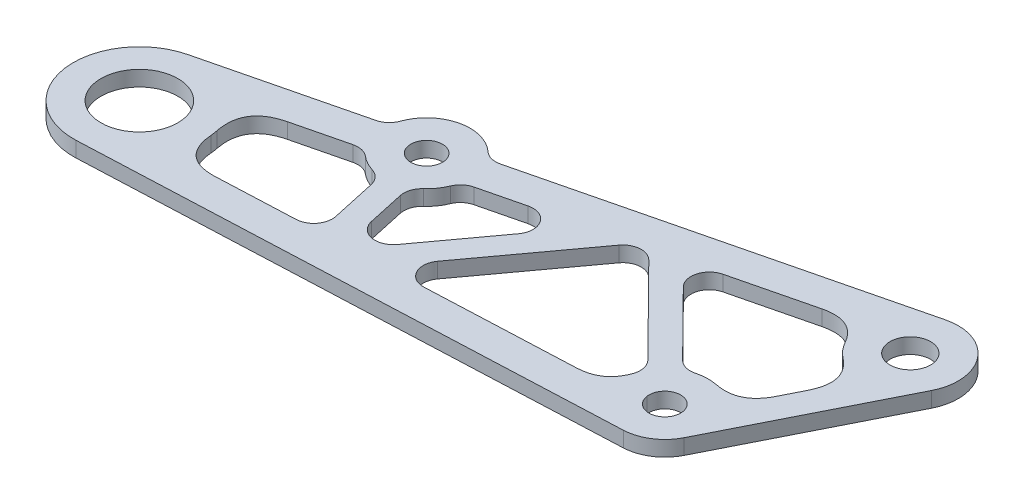
SolidWorks part; units mm, degrees
material "6061-T6 (SS)"
ref_plane "Front Plane" through (0, 0, 0) normal (0, 0, 1) x (1, 0, 0)
ref_plane "Top Plane" through (0, 0, 0) normal (0, 1, 0) x (1, 0, 0)
ref_plane "Right Plane" through (0, 0, 0) normal (1, 0, 0) x (0, 0, -1)
sketch "Sketch1" plane through (0, 0, 0) normal (0, 1, 0) x (1, 0, 0)
  line L0 (0, 0) -> (124.8778, 34.4406) construction
  line L1 (124.8778, 34.4406) -> (108.585, 0) construction
  line L2 (108.585, 0) -> (0, 0) construction
  line L3 (-3.2476, 13.2606) -> (122.5214, 44.0623)
  line L5 (116.6057, -4.036) -> (133.7266, 29.9879)
  line L6 (108.585, 0) -> (109.8191, -8.8937) construction
  line L7 (-1.8881, 7.7097) -> (123.8808, 38.5113)
  line L8 (111.5006, -1.4671) -> (128.6215, 32.5568)
  line L9 (0.3416, -7.9301) -> (108.7255, -3.2609)
  line L10 (108.585, 0) -> (80.9067, 27.9867) construction
  line L11 (108.585, 0) -> (108.585, 29.9472) construction
  line L12 (74.1927, 26.3424) -> (50.6623, -5.7623) construction
  line L13 (78.0308, 27.2823) -> (53.9142, -5.6222)
  line L14 (70.3546, 25.4024) -> (47.4105, -5.9024)
  line L15 (78.0308, 27.2823) -> (100.7231, 4.3373)
  line L16 (83.7825, 28.691) -> (104.3351, 7.9094)
  line L17 (62.4275, 10.29) -> (60.3789, 11.7916) construction
  line L18 (62.4275, 10.29) -> (64.4762, 8.7885) construction
  line L19 (94.7458, 13.9933) -> (92.9399, 12.2073) construction
  line L20 (94.7458, 13.9933) -> (96.5518, 15.7794) construction
  line L21 (114.3014, 6.9241) -> (123.2323, 24.6722)
  line L22 (0.5876, -13.6398) -> (108.9715, -8.9706)
  line L23 (9.9856, 9.3101) -> (114.9891, 35.0261)
  line L24 (12.1896, -6.1485) -> (99.9242, -2.3689)
  line L25 (12.626, 31.0376) -> (39.0947, 20.2702) construction
  line L26 (12.626, 31.0376) -> (0, 0) construction
  line L27 (39.0947, 20.2702) -> (44.8348, -6.0133) construction
  line L28 (43.4137, 12.3983) -> (47.4105, -5.9024)
  line L29 (-819.3721, 46.7661) -> (-738.0185, 246.752) construction
  line L30 (38.4507, 11.3144) -> (42.2592, -6.1243)
  line L31 (-176324.9257, 71613.2166) -> (174939.7278, -71280.061) construction
  circle A0 centre (0, 0) radius 7.9375
  circle A1 centre (124.8778, 34.4406) radius 4.191
  circle A2 centre (108.585, 0) radius 3.2639
  circle A3 centre (0, 0) radius 13.6525
  circle A4 centre (108.585, 0) radius 8.9789
  circle A5 centre (124.8778, 34.4406) radius 9.906
  arc A6 (-3.2476, 13.2606) -> (6.5337, -11.9876) centre (0, 0) ccw
  arc A7 (116.6057, -4.036) -> (108.585, -8.9789) centre (108.585, 0) cw
  arc A8 (122.5214, 44.0623) -> (133.7266, 29.9879) centre (124.8778, 34.4406) cw
  circle A9 centre (39.0947, 20.2702) radius 3.2639
  circle A10 centre (39.0947, 20.2702) radius 8.9789
  dimension "D4" = 15.875
  dimension "D5" = 6.5278
  dimension "D6" = 8.382
  dimension "D7" = 5.715
  dimension "D8" = 5.715
  dimension "D9" = 5.715
  dimension "D18" = 17.9578
  dimension "D19" = 6.5278
  dimension "D1" = 129.54
  dimension "D2" = 38.1
  dimension "D3" = 108.585
  dimension "D10" = 97.9
  dimension "D11" = 70
  dimension "D12" = 40
  dimension "D13" = 5.08
  dimension "D14" = 1.27
  dimension "D15" = 1.27
  dimension "D16" = 1.27
  dimension "D17" = 28.575
  dimension "D20" = 2.54
  dimension "D21" = 5.08
extrude "Boss-Extrude4" add sketch "Sketch1" against normal blind 3.175 contours A5 L7 A1 L8 | A5 L3 A3 L7 | A3 L9 A0 L7 | L9 A3 L7 A0 | A3 L9 L14 L24 | A4 L9 A3 L22 | A4 L24 L13 L9 | L24 L14 L9 L13 | A4 L16 L23 L15 | L14 L23 L13 L7 | L15 L23 L16 L7 | A5 L7 L16 L23 | A5 L8 A4 L5 | L7 A5 L8 A1 | A4 L8 A2 L9 | L8 A4 L9 A2 | L7 A10 | A10 L23 L14 L7 | L14 L24 L13 L23 | A10 L30 L24 L28 | L24 L30 L9 L28 | A10 L23 A9 | L7 A10 L23 A9 | A10 L7 A3 L23 | A10 L3 A3 L7 | L3 A10 | L7 A10 L3 A9 region at (3.0925, 0, -12.9166) region at (17.5549, 0, -15.5789) region at (37.7563, 0, -25.7353) region at (33.4097, 0, -19.3627) region at (55.5019, 0, 8.4889) region at (9.0069, 0, -1.2841) region at (20.5523, 0, -12.5533) region at (44.5556, 0, -22.0924) region at (82.2682, 0, -31.3107) region at (34.4779, 0, -16.435) region at (110.8898, 0, 3.5657) region at (130.8206, 0, -42.0146) region at (40.4953, 0, -14.5512) region at (122.752, 0, -13.9922) region at (26.9756, 0, 6.1507) region at (99.6799, 0, -31.9349) region at (120.3421, 0, -30.8296) region at (58.8928, 0, -21.9466) region at (42.7943, 0, -3.4344) region at (106.4195, 0, -3.3502) region at (77.2616, 0, 3.984) region at (44.6973, 0, 5.3837) region at (81.4272, 0, -27.4604) region at (73.6087, 0, -25.5456) region at (62.3569, 0, -10.1545) region at (51.1433, 0, 5.106) region at (92.1113, 0, -16.5941)
ref_plane "Plane1" through (108.585, 0, 0) normal (0.1374, 0, 0.9905) x (0.9905, 0, -0.1374)
split line "Split Line1"
sketch "Sketch2" [suppressed] plane through (0, -3.175, 0) normal (0, -1, 0) x (1, 0, 0)
  line L1 (69.4473, -23.6659) -> (60.7288, -1.2641)
  line L2 (62.8949, 2.1892) -> (101.6127, 5.2609)
  line L3 (101.2476, -37.8411) -> (79.7056, -31.0891)
  line L4 (79.2148, -26.4545) -> (98.3531, -15.6299)
  line L5 (59.9072, -25.992) -> (7.538, -8.592)
  line L6 (63.0965, -22.7173) -> (54.4829, 1.0899)
  line L7 (51.7805, 2.7463) -> (11.1946, -2.3078)
  line L8 (73.1912, -24.8791) -> (102.155, -6.1958)
  line L9 (104.5239, -35.0732) -> (102.1201, -17.4966)
  circle A0 centre (111.76, 0) radius 11.43 construction
  circle A3 centre (0, 0) radius 11.43 construction
  arc A4 (11.1946, -2.3078) -> (7.538, -8.592) centre (0, 0) cw
  arc A5 (101.6127, 5.2609) -> (102.155, -6.1958) centre (111.76, 0) ccw
  arc A6 (101.2476, -37.8411) -> (104.5239, -35.0732) centre (102.0073, -35.4173) ccw
  arc A7 (98.3531, -15.6299) -> (102.1201, -17.4966) centre (99.6035, -17.8407) cw
  arc A8 (69.4473, -23.6659) -> (73.1912, -24.8791) centre (71.8144, -22.7446) ccw
  arc A9 (60.7288, -1.2641) -> (62.8949, 2.1892) centre (63.0958, -0.3428) cw
  arc A10 (63.0965, -22.7173) -> (59.9072, -25.992) centre (60.7081, -23.5815) cw
  arc A11 (54.4829, 1.0899) -> (51.7805, 2.7463) centre (52.0944, 0.2257) ccw
  arc A12 (79.2148, -26.4545) -> (79.7056, -31.0891) centre (80.4653, -28.6654) ccw
  dimension "D1" = 2.54
  dimension "D2" = 2.54
  dimension "D3" = 2.54
  dimension "D4" = 2.54
  dimension "D5" = 2.54
  dimension "D6" = 2.54
  dimension "D7" = 2.54
extrude "Cut-Extrude2" [suppressed] cut sketch "Sketch2" against normal through all
fillet "Fillet1" radius 7.62 6 edges at (115.2605, -1.5875, -6.0049) (124.5869, -1.5875, -24.5389) (114.9891, -1.5875, -35.0261) (9.9856, -1.5875, -9.3101) (99.9242, -1.5875, 2.3689) (12.1896, -1.5875, 6.1485) conic rho 0.5
fillet "Fillet2" radius 3.81 14 edges at (104.3351, -1.5875, -7.9094) (100.7231, -1.5875, -4.3373) (84.8235, -1.5875, -27.6384) (69.1866, -1.5875, -23.8088) (41.9842, -1.5875, 4.865) (32.0429, -1.5875, -14.7121) (38.4507, -1.5875, -11.3144) (43.4137, -1.5875, -12.3983) (47.9169, -1.5875, -18.5997) (54.8762, -1.5875, 4.3096) (47.4105, -1.5875, 5.9024) (78.0308, -1.5875, -27.2823) (46.4429, -1.5875, -25.4301) (30.1937, -1.5875, -21.4506)
equation "\"x\"= .05"
